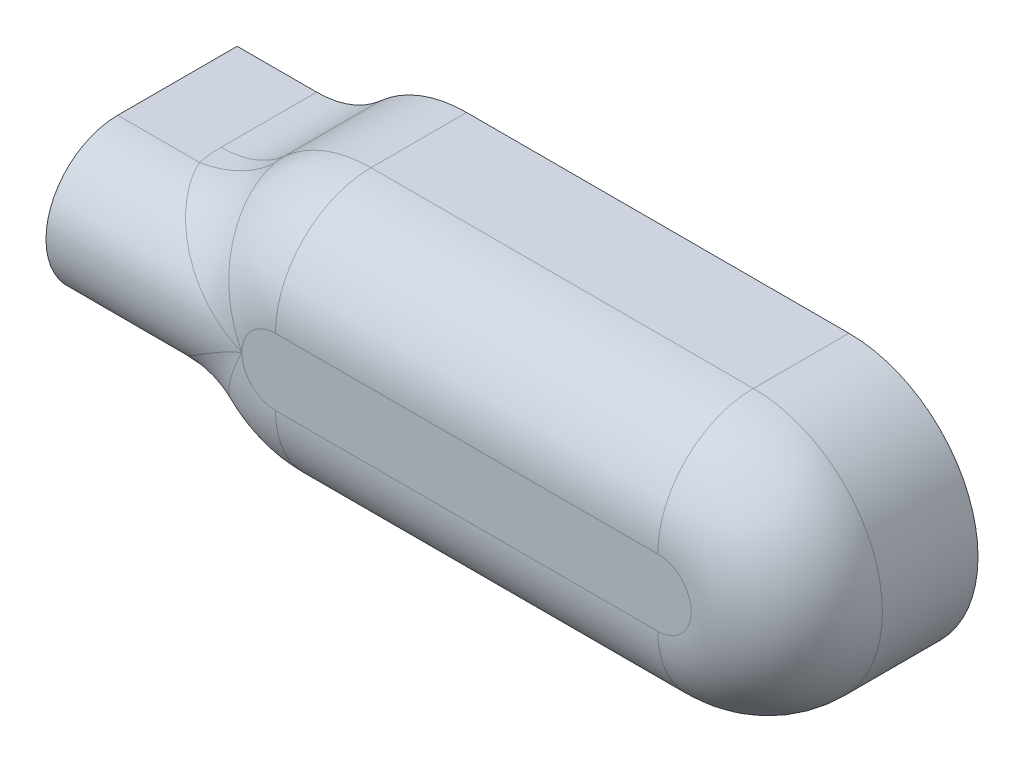
SolidWorks part; units mm, degrees
ref_plane "Front Plane" through (0, 0, 0) normal (0, 0, 1) x (1, 0, 0)
ref_plane "Top Plane" through (0, 0, 0) normal (0, 1, 0) x (1, 0, 0)
ref_plane "Right Plane" through (0, 0, 0) normal (1, 0, 0) x (0, 0, -1)
sketch "Sketch1" plane through (0, 0, 0) normal (0, 0, 1) x (1, 0, 0)
  line L0 (77.2984, 53.6856) -> (117.2984, 53.6856) construction
  line L1 (77.2984, 65.6856) -> (117.2984, 65.6856) construction
  line L2 (77.2984, 41.6856) -> (117.2984, 41.6856) construction
  line L3 (117.2984, 53.6856) -> (77.2984, 53.6856) construction
  line L4 (117.2984, 40.1856) -> (77.2984, 40.1856)
  line L5 (117.2984, 67.1856) -> (77.2984, 67.1856)
  arc A0 (77.2984, 65.6856) -> (77.2984, 41.6856) centre (77.2984, 53.6856) ccw construction
  arc A1 (117.2984, 41.6856) -> (117.2984, 65.6856) centre (117.2984, 53.6856) ccw construction
  arc A2 (77.2984, 65.6856) -> (77.2984, 41.6856) centre (77.2984, 53.6856) ccw construction
  arc A3 (117.2984, 41.6856) -> (117.2984, 65.6856) centre (117.2984, 53.6856) ccw construction
  arc A4 (117.2984, 40.1856) -> (117.2984, 67.1856) centre (117.2984, 53.6856) ccw
  arc A5 (77.2984, 67.1856) -> (77.2984, 40.1856) centre (77.2984, 53.6856) ccw
  point P3 (97.2984, 53.6856)
  point P16 (97.2984, 53.6856)
  dimension "D1" = 1.5
extrude "Boss-Extrude1" add sketch "Sketch1" along normal blind 20
sketch "Sketch2" plane through (0, 0, 0) normal (1, 0, 0) x (0, 0, -1)
  line L0 (-12.5, 53.6856) -> (7.5, 53.6856) construction
  line L1 (-12.5, 61.1856) -> (0, 61.1856)
  line L2 (-12.5, 46.1856) -> (0, 46.1856)
  line L3 (0, 40.1856) -> (0, 67.1856) construction
  line L5 (-20, 67.1856) -> (-20, 40.1856) construction
  line L7 (0, 61.1856) -> (0, 46.1856)
  line L8 (-20, 67.1856) -> (-20, 40.1856) construction
  arc A0 (-12.5, 61.1856) -> (-12.5, 46.1856) centre (-12.5, 53.6856) ccw
  point P2 (-2.5, 53.6856)
  point P10 (-20, 53.6856)
  dimension "D1" = 15
extrude "Boss-Extrude2" add sketch "Sketch2" against normal blind 24 from vertex at 77.2984 starting at point (77.2984, 40.1856, 20)
fillet "Fillet1" radius 10 5 edges at (97.2984, 40.1856, 20) (67.7525, 44.1397, 20) (67.7525, 63.2316, 20) (97.2984, 67.1856, 20) (130.7984, 53.6856, 20)
fillet "Fillet2" radius 10 6 edges at (66.0735, 46.1856, 5) (68.6663, 59.5096, 17.2256) (68.6663, 47.8617, 17.2256) (66.0735, 61.1856, 5)
shell "Shell1" thickness 1
